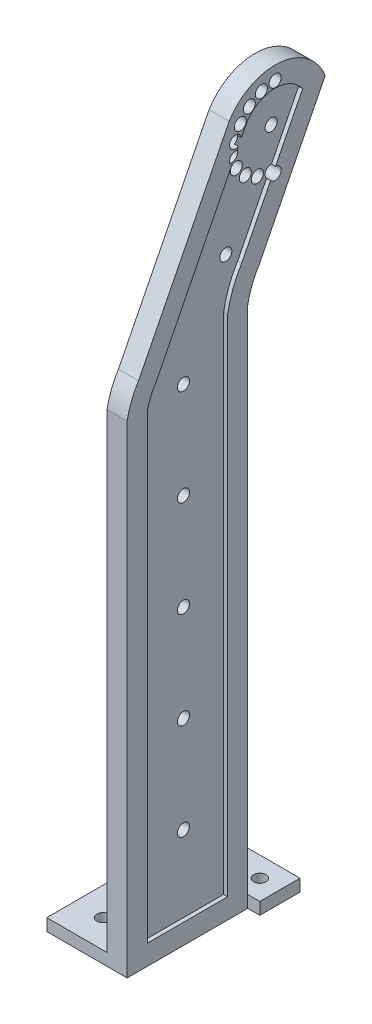
SolidWorks part; units mm, degrees
ref_plane "前视基准面" through (0, 0, 0) normal (0, 0, 1) x (1, 0, 0)
ref_plane "上视基准面" through (0, 0, 0) normal (0, 1, 0) x (1, 0, 0)
ref_plane "右视基准面" through (0, 0, 0) normal (1, 0, 0) x (0, 0, -1)
sketch "草图1" plane through (0, 0, 0) normal (1, 0, 0) x (0, 0, -1)
  line L0 (-15, 0) -> (15, 0)
  line L1 (-15, 0) -> (-15, 120)
  line L2 (15, 0) -> (15, 130)
  line L3 (17.8333, 137.2485) -> (34.2776, 169.8061)
  line L4 (-12.1667, 127.2485) -> (10.3753, 171.8787)
  line L5 (18.3925, 174.3148) -> (21.8127, 164.9179) construction
  line L7 (11.218, 143.9417) -> (10.5417, 142.6028) construction
  line L8 (21.8127, 164.9179) -> (11.9646, 166.6544) construction
  line L9 (13.1525, 169.9179) -> (21.8127, 164.9179) construction
  line L10 (11.9646, 163.1814) -> (21.8127, 164.9179) construction
  line L11 (21.8127, 164.9179) -> (13.1525, 159.9179) construction
  line L12 (21.8127, 164.9179) -> (15.3848, 172.5784) construction
  line L13 (15.3848, 157.2575) -> (21.8127, 164.9179) construction
  line L14 (21.8127, 164.9179) -> (18.3925, 155.521) construction
  line L15 (21.8127, 164.9179) -> (21.8127, 174.9179) construction
  line L16 (21.8127, 154.9179) -> (21.8127, 164.9179) construction
  arc A0 (15, 130) -> (17.8333, 137.2485) centre (34.6882, 126.4823) cw
  arc A1 (-12.1667, 127.2485) -> (-15, 120) centre (4.6882, 116.4823) ccw
  circle A2 centre (0, 23.9341) radius 1.5
  circle A3 centre (0, 47.9341) radius 1.5
  circle A4 centre (0, 71.9341) radius 1.5
  circle A5 centre (0, 95.9341) radius 1.5
  circle A7 centre (21.8127, 164.9179) radius 10 construction
  circle A8 centre (10.5417, 142.6028) radius 1.5
  circle A9 centre (0, 119.9341) radius 1.5
  arc A10 (34.2776, 169.8061) -> (10.3753, 171.8787) centre (21.8127, 164.9179) ccw
  circle A11 centre (21.8127, 164.9179) radius 1.5
  circle A13 centre (11.9646, 166.6544) radius 1.5
  circle A14 centre (11.9646, 163.1814) radius 1.5
  circle A15 centre (13.1525, 159.9179) radius 1.5
  circle A16 centre (15.3848, 157.2575) radius 1.5
  circle A17 centre (18.3925, 155.521) radius 1.5
  circle A18 centre (21.8127, 154.9179) radius 1.5
  circle A19 centre (13.1525, 169.9179) radius 1.5
  circle A20 centre (15.3848, 172.5784) radius 1.5
  circle A21 centre (18.3925, 174.3148) radius 1.5
  circle A22 centre (21.8127, 174.9179) radius 1.5
  point P3 (0, 0)
  dimension "D5" = 20
  dimension "D7" = 20
  dimension "D4" = 3
  dimension "D9" = 3
  dimension "D11" = 3
  dimension "D16" = 20
  dimension "D21" = 20
  dimension "D22" = 20
  dimension "D1" = 30
  dimension "D2" = 120
  dimension "D3" = 130
  dimension "D6" = 24
  dimension "D8" = 25
  dimension "D10" = 15
  dimension "D12" = 25
  dimension "D13" = 24
  dimension "D14" = 24
  dimension "D15" = 24
  dimension "D17" = 20
  dimension "D18" = 20
  dimension "D19" = 20
  dimension "D20" = 20
extrude "凸台-拉伸2" add sketch "草图1" against normal blind 5
ref_plane "基准面1" through (-5, 0, 0) normal (-1, 0, 0) x (0, 0, 1)
ref_plane "基准面3" through (-30, 0, 0) normal (-1, 0, 0) x (0, 0, 1)
ref_plane "基准面5" through (0, 0, 0) normal (1, 0, 0) x (0, 0, -1)
sketch "草图4" plane through (0, 0, 0) normal (1, 0, 0) x (0, 0, -1)
  line L10 (-10, 5) -> (10, 5)
  line L18 (10, 5) -> (10, 130.4183)
  line L19 (13.4775, 139.7151) -> (28.6572, 169.7687)
  line L20 (14.7389, 169.4276) -> (-7.8255, 124.7531)
  line L21 (-10, 119.5247) -> (-10, 5)
  line L22 (-10, 5) -> (10, 5)
  line L23 (10, 5) -> (10, 130.4183)
  line L24 (13.4775, 139.7151) -> (28.6572, 169.7687)
  line L25 (14.7389, 169.4276) -> (-7.8255, 124.7531)
  line L26 (-10, 119.5247) -> (-10, 5)
  arc A6 (13.4775, 139.7151) -> (10, 130.4183) centre (34.6882, 126.4823) ccw
  arc A7 (28.6572, 169.7687) -> (14.7389, 169.4276) centre (21.8127, 164.9179) ccw
  arc A8 (-7.8255, 124.7531) -> (-10, 119.5247) centre (4.6882, 116.4823) ccw
  arc A9 (13.4775, 139.7151) -> (10, 130.4183) centre (34.6882, 126.4823) ccw
  arc A13 (28.6572, 169.7687) -> (14.7389, 169.4276) centre (21.8127, 164.9179) ccw
  arc A14 (-7.8255, 124.7531) -> (-10, 119.5247) centre (4.6882, 116.4823) ccw
  dimension "D1" = 5
extrude "切除-拉伸1" cut sketch "草图4" against normal blind 1
ref_plane "基准面6" through (0, 0, 0) normal (0, -1, 0) x (-1, 0, 0)
sketch "草图5" plane through (0, 0, 0) normal (0, -1, 0) x (-1, 0, 0)
  line L0 (0, -15) -> (20, -15)
  line L1 (20, -15) -> (20, 15)
  line L3 (0, 15) -> (0, -15)
  line L4 (0, 15) -> (-3, 15)
  line L5 (-3, 15) -> (-3, 25)
  line L6 (-3, 25) -> (20, 25)
  line L9 (20, 15) -> (20, 25)
  dimension "D1" = 20
  dimension "D2" = 30
  dimension "D3" = 20
  dimension "D6" = 3
  dimension "D7" = 10
extrude "凸台-拉伸3" add sketch "草图5" against normal blind 3
sketch "草图6" plane through (0, 0, 0) normal (0, -1, 0) x (1, 0, 0)
  line L1 (-20, 15) -> (0, 15) construction
  line L3 (-20, 15) -> (-20, -25) construction
  line L4 (-20, -25) -> (3, -25) construction
  line L6 (3, -25) -> (3, -15) construction
  circle A1 centre (-13, 8) radius 1.55
  circle A3 centre (-2, -20) radius 1.55
  circle A4 centre (-13, -3) radius 1.55
  dimension "D1" = 3.1
  dimension "D4" = 3.1
  dimension "D2" = 3.1
  dimension "D3" = 11
  dimension "D5" = 7
  dimension "D6" = 7
  dimension "D7" = 5
  dimension "D9" = 5
extrude "切除-拉伸2" cut sketch "草图6" against normal blind 10
sketch "草图7" plane through (-5, 0, 0) normal (-1, 0, 0) x (0, 0, 1)
  line L0 (15, 3) -> (-15, 3) construction
  line L5 (-11.8, 3) -> (-8.8, 3)
  line L6 (-11.8, 3) -> (-11.8, 44)
  line L7 (-11.8, 44) -> (-8.8, 44)
  line L8 (-8.8, 3) -> (-8.8, 44)
  line L9 (-15, 3) -> (-15, 130) construction
  dimension "D1" = 3
  dimension "D2" = 41
  dimension "D3" = 3.2
extrude "凸台-拉伸4" add sketch "草图7" along normal blind 13
sketch "草图9" plane through (0, 0, -11.8) normal (0, 0, -1) x (-1, 0, 0)
  line L0 (18, 44) -> (5, 44) construction
  line L1 (5, 44) -> (18, 44)
  arc A0 (18, 44) -> (5, 44) centre (11.5, 44) ccw
extrude "凸台-拉伸5" add sketch "草图9" against normal blind 3
sketch "草图10" plane through (0, 0, -11.8) normal (0, 0, -1) x (-1, 0, 0)
  circle A0 centre (11.5, 44) radius 1.6
  circle A1 centre (11.5, 7) radius 1.6
  dimension "D1" = 3.2
  dimension "D2" = 3.2
  dimension "D3" = 37
extrude "切除-拉伸3" cut sketch "草图10" against normal blind 3
